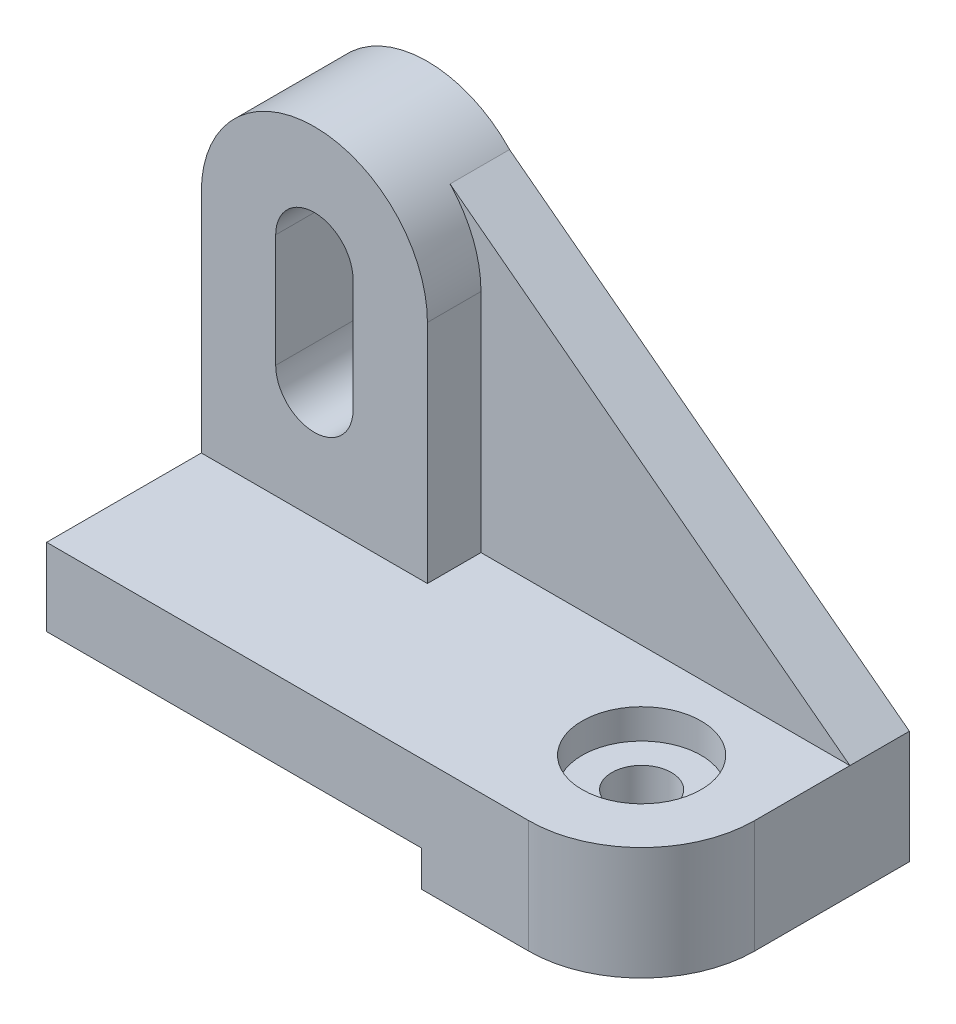
SolidWorks part; units mm, degrees
ref_plane "Front Plane" through (0, 0, 0) normal (0, 0, 1) x (1, 0, 0)
ref_plane "Top Plane" through (0, 0, 0) normal (0, 1, 0) x (1, 0, 0)
ref_plane "Right Plane" through (0, 0, 0) normal (1, 0, 0) x (0, 0, -1)
sketch "Sketch1" plane through (0, 0, 0) normal (0, 0, 1) x (1, 0, 0)
  line L0 (0, 0) -> (0, 130)
  line L1 (0, 130) -> (1000, 130)
  line L2 (1000, 130) -> (1000, -60)
  line L3 (1000, -60) -> (630, -60)
  line L4 (630, -60) -> (630, 0)
  line L5 (630, 0) -> (0, 0)
  point P5 (0, 0)
  dimension "D1" = 130
  dimension "D2" = 60
  dimension "D3" = 1000
  dimension "D4" = 630
  dimension "D5" = 190
extrude "Boss-Extrude1" add sketch "Sketch1" along normal blind 450
fillet "Fillet2" radius 190 1 edges at (1000, 35, 450)
sketch "Sketch2" plane through (0, 130, 0) normal (0, 1, 0) x (1, 0, 0)
  circle A0 centre (810, -260) radius 100
  point P3 (0, 0)
  dimension "D1" = 200
extrude "Cut-Extrude2" cut sketch "Sketch2" against normal blind 50 contours A0
sketch "Sketch6" plane through (0, 80, 0) normal (0, 1, 0) x (1, 0, 0)
  circle A0 centre (810, -260) radius 50
  dimension "D1" = 100
extrude "Cut-Extrude4" cut sketch "Sketch6" against normal blind 506 and the other way blind 309
sketch "Sketch8" plane through (0, 0, 0) normal (0, 0, -1) x (-1, 0, 0)
  line L0 (0, 130) -> (0, 510)
  line L1 (-380, 130) -> (-380, 510)
  line L2 (-1000, 130) -> (0, 130) construction
  line L3 (-1000, 130) -> (-336.5857, 630.8827)
  line L4 (-190, 510) -> (-190, 320) construction
  line L5 (-125, 510) -> (-125, 320)
  line L6 (-255, 510) -> (-255, 320)
  arc A0 (0, 510) -> (-380, 510) centre (-190, 510) ccw
  arc A1 (-125, 510) -> (-255, 510) centre (-190, 510) ccw
  arc A2 (-255, 320) -> (-125, 320) centre (-190, 320) ccw
  point P12 (-190, 415)
  point P18 (0, 0)
  line M10 (0, 130) -> (-1000, 130)
  dimension "D1" = 190
  dimension "D3" = 65
  dimension "D2" = 570
  dimension "D4" = 190
extrude "Boss-Extrude2" add sketch "Sketch8" against normal blind 190 contours L0 A0 L1 A2 L6 A1 L5 M10 region at (190, 136.8505, 0)
sketch "Sketch10" plane through (0, 0, 0) normal (0, 0, -1) x (-1, 0, 0)
  line L0 (-1000, 130) -> (-328.0365, 640.56)
  arc A0 (0, 510) -> (-380, 510) centre (-190, 510) ccw construction
rib "Rib9" sketch "Sketch10" sketch "Sketch10" thickness 100 extrusion direction parallel to sketch draft on no parameters "D1"=100
